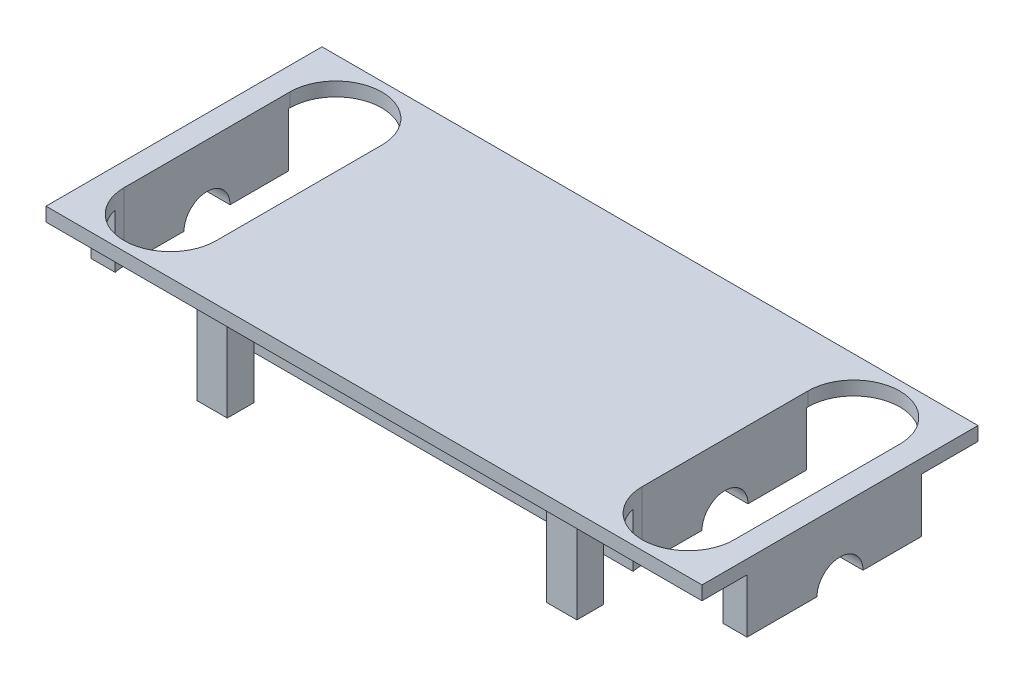
SolidWorks part; units mm, degrees
ref_plane "Front Plane" through (0, 0, 0) normal (0, 0, 1) x (1, 0, 0)
ref_plane "Top Plane" through (0, 0, 0) normal (0, 1, 0) x (1, 0, 0)
ref_plane "Right Plane" through (0, 0, 0) normal (1, 0, 0) x (0, 0, -1)
sketch "Sketch1" plane through (0, 0, 0) normal (0, 1, 0) x (1, 0, 0)
  line L0 (-5.842, 0) -> (-7.112, -1.2443)
  line L1 (-7.112, -1.2443) -> (-7.112, -8.6103)
  line L2 (-7.112, -8.6103) -> (1.27, -8.6103)
  line L3 (1.27, -8.6103) -> (1.27, -1.2443)
  line L4 (1.27, -1.2443) -> (0, 0)
  line L5 (0, 0) -> (-5.842, 0)
  line L6 (90.678, 0) -> (89.408, -1.2443)
  line L7 (89.408, -1.2443) -> (89.408, -8.6103)
  line L8 (89.408, -8.6103) -> (97.79, -8.6103)
  line L9 (97.79, -8.6103) -> (97.79, -1.2443)
  line L10 (97.79, -1.2443) -> (96.52, 0)
  line L11 (96.52, 0) -> (90.678, 0)
  point P2 (93.599, -8.6103)
  point P21 (-2.921, -8.6103)
  dimension "D1" = 7.366
  dimension "D2" = 8.382
  dimension "D3" = 1.778
  dimension "D4" = 5.842
  dimension "D5" = 96.52
extrude "Guide rods" add sketch "Sketch1" along normal blind 25.4
sketch "Sketch2" plane through (0, 25.4, 0) normal (0, 1, 0) x (1, 0, 0)
  line L0 (-7.112, -1.2443) -> (-7.112, -8.6103) construction
  line L1 (-45.212, -12.1663) -> (135.89, -12.1663)
  line L2 (-45.212, -12.1663) -> (-45.212, 64.0337)
  line L3 (-45.212, 64.0337) -> (135.89, 64.0337)
  line L4 (135.89, -12.1663) -> (135.89, 64.0337)
  line L5 (-7.112, -8.6103) -> (1.27, -8.6103) construction
  line L6 (97.79, -8.6103) -> (97.79, -1.2443) construction
  dimension "D1" = 38.1
  dimension "D2" = 3.556
  dimension "D3" = 38.1
  dimension "D4" = 76.2
extrude "baseplate" add sketch "Sketch2" along normal blind 3.81
sketch "Sketch3" plane through (-45.212, 0, 0) normal (-1, 0, 0) x (0, 0, 1)
  line L0 (-48.3705, 25.4) -> (-0.2633, 25.4)
  line L2 (-0.2633, 25.4) -> (-0.2633, 10.4877)
  line L3 (-0.2633, 10.4877) -> (-19.5837, 10.4877)
  line L7 (-32.2837, 10.4877) -> (-48.3705, 10.4877)
  line L8 (-48.3705, 10.4877) -> (-48.3705, 25.4)
  line L9 (12.1663, 29.21) -> (12.1663, 25.4) construction
  line L10 (-64.0337, 25.4) -> (12.1663, 25.4) construction
  arc A0 (-19.5837, 10.4877) -> (-32.2837, 10.4877) centre (-25.9337, 10.4877) ccw
  dimension "D1" = 6.35
  dimension "D2" = 38.1
extrude "rod cup" add sketch "Sketch3" against normal up to surface (181.102 mm away) up to face at (135.89, 27.305, -25.9337)
sketch "Sketch4" plane through (0, 29.21, 0) normal (0, 1, 0) x (1, 0, 0)
  line L0 (-26.162, 48.7937) -> (-26.162, 3.0737) construction
  line L1 (-13.462, 48.7937) -> (-13.462, 3.0737)
  line L2 (-38.862, 48.7937) -> (-38.862, 3.0737)
  line L3 (-45.212, 64.0337) -> (-45.212, -12.1663) construction
  line L5 (-45.212, -12.1663) -> (135.89, -12.1663) construction
  line L6 (135.89, 64.0337) -> (-45.212, 64.0337) construction
  line L7 (45.339, 64.0337) -> (45.339, -12.1663) construction
  line L8 (116.84, 48.7937) -> (116.84, 3.0737) construction
  line L9 (104.14, 48.7937) -> (104.14, 3.0737)
  line L10 (129.54, 48.7937) -> (129.54, 3.0737)
  arc A0 (-13.462, 48.7937) -> (-38.862, 48.7937) centre (-26.162, 48.7937) ccw
  arc A1 (-38.862, 3.0737) -> (-13.462, 3.0737) centre (-26.162, 3.0737) ccw
  arc A2 (104.14, 48.7937) -> (129.54, 48.7937) centre (116.84, 48.7937) cw
  arc A3 (129.54, 3.0737) -> (104.14, 3.0737) centre (116.84, 3.0737) cw
  point P2 (-26.162, 25.9337)
  point P17 (116.84, 25.9337)
  dimension "D1" = 15.24
  dimension "D2" = 25.4
  dimension "D3" = 6.35
  dimension "D4" = 15.24
extrude "Handles" cut sketch "Sketch4" against normal through all
